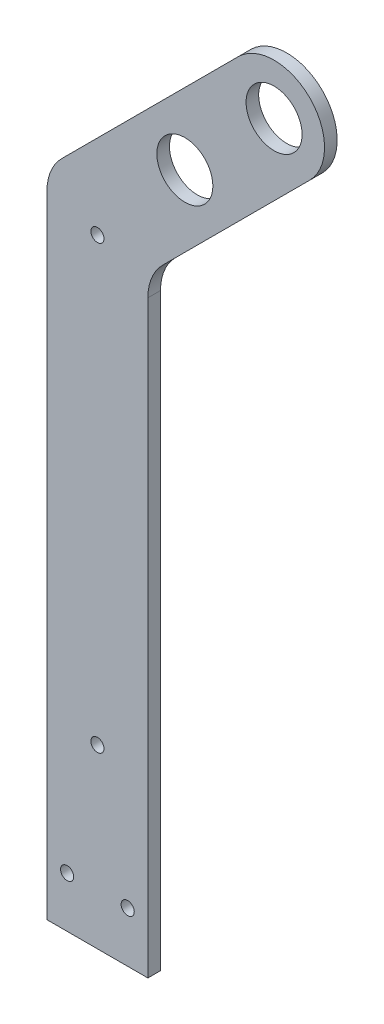
SolidWorks part; units mm, degrees
material "6061 合金"
ref_plane "前视基准面" through (0, 0, 0) normal (0, 0, 1) x (1, 0, 0)
ref_plane "上视基准面" through (0, 0, 0) normal (0, 1, 0) x (1, 0, 0)
ref_plane "右视基准面" through (0, 0, 0) normal (1, 0, 0) x (0, 0, -1)
other "Configuration Table"
sketch "草图1" plane through (0, 0, 0) normal (0, 0, 1) x (1, 0, 0)
  circle A0 centre (0, 0) radius 20
  circle A1 centre (0, 0) radius 11.1
  dimension "D1" = 40
  dimension "D2" = 22.2
extrude "凸台-拉伸1" add sketch "草图1" along normal blind 60 contours A1 | A0 region at (0, 0, 0)
ref_plane "基准面1" through (0, 0, 30) normal (0, 0, 1) x (1, 0, 0)
sketch "草图2" plane through (0, 0, 30) normal (0, 0, 1) x (1, 0, 0)
  line L0 (0, 0) -> (-70, -70) construction
  line L1 (-70, -70) -> (-70, -320) construction
  line L2 (0, -57.3148) -> (0, 49.9409) construction
  line L3 (-56.8582, 0) -> (46.4003, 0) construction
  line L4 (-14.1421, 14.1421) -> (-90, -61.7157)
  line L5 (14.1421, -14.1421) -> (-50, -78.2843)
  line L6 (-90, -61.7157) -> (-90, -320)
  line L7 (-50, -78.2843) -> (-50, -320)
  line L8 (-90, -320) -> (-50, -320)
  circle A2 centre (0, 0) radius 20 construction
  arc A3 (-14.1421, 14.1421) -> (14.1421, -14.1421) centre (0, 0) ccw
  dimension "D1" = 45
  dimension "D2" = 250
  dimension "D3" = 70
  dimension "D4" = 40
  dimension "D5" = 40
extrude "凸台-拉伸2" add sketch "草图2" along normal mid plane 60 contours L7 L8 L6 L4 A3 L5
sketch "草图4" plane through (0, 0, 60) normal (0, 0, 1) x (1, 0, 0)
  line L0 (-90, -61.7157) -> (-90, -320) construction
  line L1 (-90, -290) -> (-50, -290)
  line L2 (-90, -290) -> (-90, -350)
  line L4 (-50, -290) -> (-50, -350)
  line L5 (-50, -78.2843) -> (-50, -320) construction
  line L6 (-90, -320) -> (-50, -320) construction
  arc A0 (-90, -350) -> (-50, -350) centre (-70, -350) ccw
  circle A1 centre (-70, -350) radius 11
  dimension "D3" = 22
  dimension "D1" = 30
  dimension "D2" = 30
extrude "凸台-拉伸3" add sketch "草图4" along normal blind 5
mirror "镜向1" about plane through (0, 0, 30) normal (0, 0, 1) of "凸台-拉伸3"
sketch "草图5" plane through (0, 0, 0) normal (0, 1, 0) x (1, 0, 0)
  line L0 (0, 0) -> (0, -78.0582) construction
ref_plane "基准面2" through (-70, 0, 0) normal (-1, 0, 0) x (0, 0, 1)
sketch "草图7" plane through (-70, 0, 0) normal (-1, 0, 0) x (0, 0, 1)
  line L0 (-34.1239, -350) -> (109.535, -350) construction
sketch "草图8" plane through (0, 0, 60) normal (0, 0, 1) x (1, 0, 0)
  line L0 (0, 0) -> (-70, -70) construction
  circle A0 centre (-35.3553, -35.3553) radius 11.1
  dimension "D1" = 22.2
  dimension "D2" = 50
extrude "切除-拉伸1" cut sketch "草图8" against normal blind 100
fillet "圆角4" radius 20 2 edges at (-90, -61.7157, 30) (-50, -78.2843, 30)
fillet "圆角1" [suppressed] radius 50
fillet "圆角2" [suppressed] radius 3
sketch "草图9" plane through (0, 0, 65) normal (0, 0, 1) x (1, 0, 0)
  circle A0 centre (-70, -350) radius 13
  dimension "D1" = 26
extrude "切除-拉伸2" [suppressed] cut sketch "草图9" against normal blind 0.75
sketch "草图10" plane through (0, 0, -5) normal (0, 0, -1) x (-1, 0, 0)
  circle A0 centre (70, -350) radius 13
  dimension "D1" = 26
extrude "切除-拉伸3" [suppressed] cut sketch "草图10" against normal blind 0.75 contours A0
sketch "草图11" plane through (-90, 0, 0) normal (-1, 0, 0) x (0, 0, 1)
  circle A0 centre (48.5, -118.9949) radius 2.75
  circle A1 centre (48.5, -183.9949) radius 2.75
  circle A2 centre (48.5, -248.9949) radius 2.75
  circle A3 centre (11.5, -248.9949) radius 2.75
  circle A4 centre (11.5, -183.9949) radius 2.75
  circle A5 centre (11.5, -118.9949) radius 2.75
  dimension "D1" = 5.5
extrude "切除-拉伸4" [suppressed] cut sketch "草图11" against normal through all contours A1 | A2 | A0 | A3 | A4 | A5
sketch "草图12" [suppressed] plane through (-90, 0, 0) normal (-1, 0, 0) x (0, 0, 1)
  line L0 (30, -62.0134) -> (30, -339.6946) construction
  line L1 (10, -128.9949) -> (50, -128.9949)
  line L2 (10, -128.9949) -> (10, -173.9949)
  line L3 (10, -173.9949) -> (50, -173.9949)
  line L4 (50, -128.9949) -> (50, -173.9949)
  line L5 (10, -193.9949) -> (50, -193.9949)
  line L6 (10, -193.9949) -> (10, -238.9949)
  line L7 (10, -238.9949) -> (50, -238.9949)
  line L8 (50, -193.9949) -> (50, -238.9949)
  line L9 (10, -258.9949) -> (50, -258.9949)
  line L10 (10, -258.9949) -> (10, -290)
  line L11 (10, -290) -> (50, -290)
  line L12 (50, -258.9949) -> (50, -290)
  line L13 (19.5, -173.9949) -> (40.5, -173.9949)
  line L14 (19.5, -173.9949) -> (19.5, -193.9949)
  line L15 (19.5, -193.9949) -> (40.5, -193.9949)
  line L16 (40.5, -173.9949) -> (40.5, -193.9949)
  line L17 (19.5, -238.9949) -> (40.5, -238.9949)
  line L18 (19.5, -238.9949) -> (19.5, -258.9949)
  line L19 (19.5, -258.9949) -> (40.5, -258.9949)
  line L20 (40.5, -238.9949) -> (40.5, -258.9949)
  line L21 (60, -82.4264) -> (60, -290) construction
  line L22 (0, -290) -> (0, -82.4264) construction
  line L23 (57, -320) -> (3, -320) construction
  circle A0 centre (48.5, -118.9949) radius 2.75 construction
  circle A1 centre (48.5, -183.9949) radius 2.75 construction
  circle A2 centre (48.5, -248.9949) radius 2.75 construction
  dimension "D1" = 10
  dimension "D2" = 10
  dimension "D3" = 10
  dimension "D4" = 8
  dimension "D5" = 10
  dimension "D6" = 10
  dimension "D7" = 10
  dimension "D8" = 30
extrude "减重" [suppressed] cut sketch "草图12" against normal through all contours L0 L1 L2 L3 | L15 L0 L17 L7 L8 L5 | L0 L5 L6 L7 | L19 L0 L11 L12 L9 | L0 L9 L10 L11 | L1 L0 L13 L3 L4
fillet "圆角3" [suppressed] radius 3
sketch "草图13" plane through (0, 0, 60) normal (0, 0, 1) x (1, 0, 0)
  circle A0 centre (0, 0) radius 13
  circle A1 centre (-35.3553, -35.3553) radius 13
  dimension "D1" = 26
  dimension "D2" = 26
extrude "切除-拉伸6" [suppressed] cut sketch "草图13" against normal blind 1.75
sketch "草图14" plane through (0, 0, 0) normal (0, 0, -1) x (-1, 0, 0)
  circle A0 centre (0, 0) radius 13
  circle A1 centre (35.3553, -35.3553) radius 13
  dimension "D1" = 26
  dimension "D2" = 26
extrude "切除-拉伸7" [suppressed] cut sketch "草图14" against normal blind 1.75
sketch "草图15" [suppressed] plane through (0, 0, 0) normal (0, 0, -1) x (-1, 0, 0)
  line L0 (0, 0) -> (70, -350) construction
  line L1 (56.2719, -67.2005) -> (60.1942, -86.8121) construction
  line L2 (70, -350) -> (204.3541, -323.1292) construction
  circle A0 centre (56.2719, -67.2005) radius 2.75
  circle A1 centre (75.2172, -73.6095) radius 2.75
  circle A2 centre (60.1942, -86.8121) radius 2.75
  dimension "D1" = 5.5
  dimension "D2" = 20
  dimension "D3" = 20
  dimension "D4" = 20
  dimension "D5" = 42
  dimension "D6" = 270
extrude "切除-拉伸8" [suppressed] cut sketch "草图15" against normal through all contours A2 | A0 | A1
ref_plane "小腿主干连杆面" through (0, 0, 0) normal (0.9806, -0.1961, 0) x (0, 0, -1)
ref_plane "小腿主干对称面" through (0, 0, 30) normal (0, 0, -1) x (-1, 0, 0)
sketch "草图16" plane through (0, 0, 60) normal (0, 0, 1) x (1, 0, 0)
  line L0 (0, 0) -> (-70, -350)
  line L1 (-35.3553, -35.3553) -> (0, 0)
sketch "草图17" plane through (0, 0, 60) normal (0, 0, 1) x (1, 0, 0)
  line L0 (0, 0) -> (-70, -350) construction
  line L1 (118.6974, 32.5948) -> (32.9122, -396.3312) construction
  line L2 (92.7764, -97.0102) -> (20.2919, -82.5133)
  line L3 (73.1648, -195.0683) -> (0.6803, -180.5713)
  circle A0 centre (20.2919, -82.5133) radius 46
  circle A1 centre (0.6803, -180.5713) radius 46
  dimension "D3" = 92
  dimension "D4" = 92
  dimension "D1" = 110
  dimension "D2" = 73.92
  dimension "D5" = 180
  dimension "D6" = 280
sketch "草图18" plane through (0, 0, 60) normal (0, 0, 1) x (1, 0, 0)
  line L1 (14.1421, -14.1421) -> (-44.1421, -72.4264) construction
  line L3 (14.1421, -14.1421) -> (-44.1421, -72.4264)
  line L4 (15.4873, -12.6548) -> (52.8188, -49.9864)
  line L5 (-50, -128.5133) -> (20.2919, -128.5133)
  line L10 (-90, -290) -> (-50, -290)
  line L11 (-50, -290) -> (-50, -86.5685)
  line L12 (-44.1421, -72.4264) -> (14.1421, -14.1421)
  line L13 (-14.1421, 14.1421) -> (-84.1421, -55.8579)
  line L14 (-90, -70) -> (-90, -290)
  line L16 (-50, -128.5133) -> (-50, -86.5685)
  line L17 (-44.1421, -72.4264) -> (14.1421, -14.1421)
  circle A0 centre (20.2919, -82.5133) radius 46 construction
  arc A1 (14.1421, -14.1421) -> (-14.1421, 14.1421) centre (0, 0) ccw construction
  arc A2 (14.1421, -14.1421) -> (-14.1421, 14.1421) centre (0, 0) ccw
  arc A3 (14.1421, -14.1421) -> (15.4873, -12.6548) centre (0, 0) ccw
  arc A4 (20.2919, -128.5133) -> (52.8188, -49.9864) centre (20.2919, -82.5133) ccw
  circle A5 centre (20.2919, -82.5133) radius 35
  arc A9 (-84.1421, -55.8579) -> (-90, -70) centre (-70, -70) ccw
  arc A10 (-84.1421, -55.8579) -> (-90, -70) centre (-70, -70) ccw
  arc A11 (-44.1421, -72.4264) -> (-50, -86.5685) centre (-30, -86.5685) ccw
  arc A12 (-44.1421, -72.4264) -> (-50, -86.5685) centre (-30, -86.5685) ccw
  line M14 (-50, -290) -> (-50, -86.5685)
  line M15 (-44.1421, -72.4264) -> (14.1421, -14.1421)
  arc M16 (14.1421, -14.1421) -> (-14.1421, 14.1421) centre (0, 0) ccw
  arc M22 (-50, -86.5685) -> (-44.1421, -72.4264) centre (-30, -86.5685) cw
  dimension "D2" = 70
  dimension "D1" = 0
extrude "凸台-拉伸4" add sketch "草图18" against normal blind 5 from offset 25 contours L5 A4 L4 A5 M16 M15 M22 M14 region at (16.0508, -14.5165, 60) offset against normal yes
sketch "草图19" plane through (0, 0, 0) normal (0, 0, -1) x (-1, 0, 0)
  line L0 (50, -86.5685) -> (50, -290) construction
  line L1 (50, -134.5713) -> (50, -226.5713)
  line L2 (-0.6803, -134.5713) -> (50, -134.5713)
  line L3 (-0.6803, -226.5713) -> (50, -226.5713)
  circle A0 centre (-0.6803, -180.5713) radius 46 construction
  arc A1 (-0.6803, -134.5713) -> (-0.6803, -226.5713) centre (-0.6803, -180.5713) ccw
  circle A2 centre (-0.6803, -180.5713) radius 35
  dimension "D1" = 70
extrude "凸台-拉伸5" add sketch "草图19" against normal blind 5 from offset 25 offset against normal yes
fillet "圆角5" radius 10 2 edges at (-50, -226.5713, 27.5) (-50, -128.5133, 32.5)
sketch "草图21" plane through (0, 0, 65) normal (0, 0, 1) x (1, 0, 0)
  line L0 (-70, -350) -> (-70, -6.9331) construction
  circle A0 centre (-70, -75) radius 2.6
  circle A1 centre (-70, -250) radius 2.6
  circle A2 centre (-58, -300) radius 2.6
  circle A3 centre (-82, -300) radius 2.6
  dimension "D1" = 5.2
  dimension "D2" = 12
  dimension "D3" = 50
  dimension "D4" = 100
  dimension "D5" = 175
extrude "切除-拉伸9" cut sketch "草图21" against normal through all both and the other way through all
sketch "草图22" plane through (-90, 0, 0) normal (-1, 0, 0) x (0, 0, 1)
  line L0 (-5, -350) -> (-5, -370) construction
  line L5 (-5, -386.4605) -> (40, -386.4605)
  line L6 (-5, -386.4605) -> (-5, 64.9179)
  line L7 (-5, 64.9179) -> (40, 64.9179)
  line L8 (40, -386.4605) -> (40, 64.9179)
  line L10 (65, -370) -> (45, -370)
  line L11 (65, -370) -> (65, 61.088)
  line L12 (65, 61.088) -> (45, 61.088)
  line L13 (45, -370) -> (45, 61.088)
  dimension "D1" = 20
  dimension "D2" = 5
extrude "切除-拉伸10" cut sketch "草图22" against normal through all both contours L8 L7 L6 L5 | L13 L12 L11 L10
